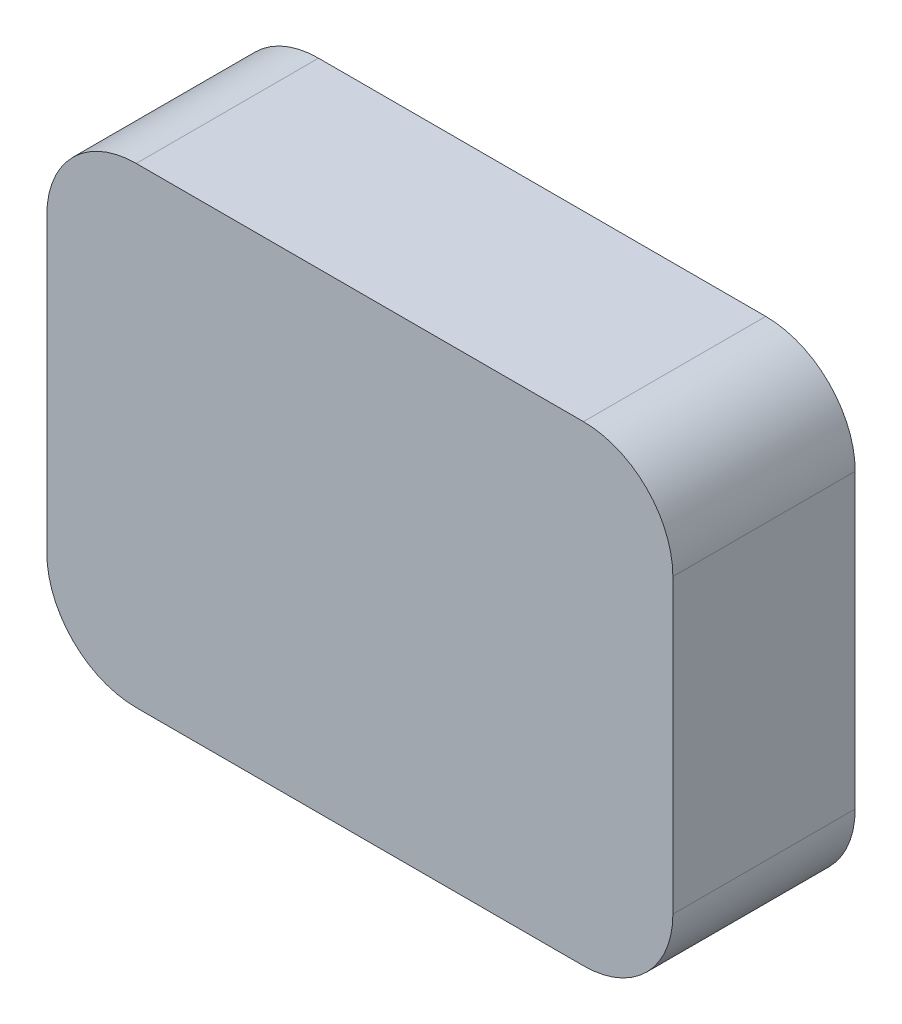
SolidWorks part; units mm, degrees
ref_plane "Plan de face" through (0, 0, 0) normal (0, 0, 1) x (1, 0, 0)
ref_plane "Plan de dessus" through (0, 0, 0) normal (0, 1, 0) x (1, 0, 0)
ref_plane "Plan de droite" through (0, 0, 0) normal (1, 0, 0) x (0, 0, -1)
sketch "Esquisse1" plane through (0, 0, 0) normal (0, 0, 1) x (1, 0, 0)
  line L1 (-26, 27) -> (26, 27)
  line L2 (-36, 17) -> (-36, -17)
  line L3 (-26, -27) -> (26, -27)
  line L4 (36, 17) -> (36, -17)
  line L5 (-36, 27) -> (36, -27) construction
  line L6 (-36, -27) -> (36, 27) construction
  arc A0 (-36, -17) -> (-26, -27) centre (-26, -17) ccw
  arc A1 (26, -27) -> (36, -17) centre (26, -17) ccw
  arc A2 (26, 27) -> (36, 17) centre (26, 17) cw
  arc A3 (-26, 27) -> (-36, 17) centre (-26, 17) ccw
  point P0 (0, 0)
  dimension "D1" = 10
  dimension "D2" = 52
  dimension "D3" = 34
sketch "profil" plane through (0, 0, 0) normal (1, 0, 0) x (0, 0, -1)
  line L0 (0, -25.5219) -> (4.1106, -25.5219)
  line L1 (4.1106, -25.5219) -> (10, -21)
  line L3 (10, -27) -> (0, -27)
  line L4 (0, -27) -> (0, -25.5219)
  line L6 (0, -17) -> (0, -27) construction
  line L7 (0, -27) -> (0, 27) construction
  line L10 (10, -21) -> (10, -27) construction
  line L11 (10, -24) -> (12.7162, -24) construction
  line L12 (10, -25.7405) -> (10, -27) construction
  line L15 (10, -27) -> (10, -26.6)
  line L16 (10, -26.6) -> (9.8, -26.6)
  line L17 (9.8, -26.6) -> (9.8, -25.8)
  line L18 (9.8, -25.8) -> (10, -25.8)
  line L20 (10, -25.8) -> (10, -25.4)
  line L21 (10, -21) -> (10, -21.4)
  line L22 (10, -21.4) -> (9.8, -21.4)
  line L23 (9.8, -21.4) -> (9.8, -22.2)
  line L24 (9.8, -22.2) -> (10, -22.2)
  line L25 (10, -22.2) -> (10, -22.6)
  line L39 (10, -22.6) -> (10.4, -22.6)
  line L54 (10.4, -22.6) -> (10.4, -23)
  line L55 (10.4, -23) -> (10.8, -23)
  line L56 (10.8, -23) -> (10.8, -23.4)
  line L57 (10.8, -23.4) -> (11.2, -23.4)
  line L58 (11.2, -23.4) -> (11.2, -23.8)
  line L59 (11.2, -23.8) -> (11.6, -23.8)
  line L60 (11.6, -23.8) -> (11.6, -24.2)
  line L61 (11.6, -24.2) -> (11.2, -24.2)
  line L62 (11.2, -24.2) -> (11.2, -24.6)
  line L63 (11.2, -24.6) -> (10.8, -24.6)
  line L64 (10.8, -24.6) -> (10.8, -25)
  line L65 (10.8, -25) -> (10.4, -25)
  line L66 (10.4, -25) -> (10.4, -25.4)
  line L67 (10.4, -25.4) -> (10, -25.4)
  point P39 (10.3628, -25)
  dimension "D3" = 10
  dimension "D4" = 6
  dimension "D5" = 0.8
  dimension "D7" = 0.4
  dimension "D1" = 0.4
  dimension "D8" = 0.4
sweep "Balayage1" add profiles "profil" path "Esquisse1"
extrude "Boss.-Extru.1" add sketch "Esquisse1<3>" along normal blind 1.2
sketch "Esquisse1<3>" plane through (0, 0, 0) normal (0, 0, 1) x (1, 0, 0) same geometry as "Esquisse1"
fillet "Congé1" radius 2 9 edges at (-32.0259, 23.0259, 0) (-34.5219, 0, 0) (-32.0259, -23.0259, 0) (-13, -25.5219, 0) (13, -25.5219, 0) (32.0259, -23.0259, 0) (34.5219, 0, 0) (32.0259, 23.0259, 0) (0, 25.5219, 0)
sketch "Esquisse2" plane through (0, 0, 0) normal (0, 0, 1) x (1, 0, 0)
  line L8 (36.4, -17) -> (36.4, 17)
  line L9 (-26, -27.4) -> (26, -27.4)
  line L10 (-36.4, 17) -> (-36.4, -17)
  line L11 (26, 27.4) -> (-26, 27.4)
  line L12 (36.4, -17) -> (36.4, 17)
  line L13 (-26, -27.4) -> (26, -27.4)
  line L14 (-36.4, 17) -> (-36.4, -17)
  line L15 (26, 27.4) -> (-26, 27.4)
  arc A8 (36.4, 17) -> (26, 27.4) centre (26, 17) ccw
  arc A9 (26, -27.4) -> (36.4, -17) centre (26, -17) ccw
  arc A10 (-36.4, -17) -> (-26, -27.4) centre (-26, -17) ccw
  arc A11 (-26, 27.4) -> (-36.4, 17) centre (-26, 17) ccw
  arc A12 (36.4, 17) -> (26, 27.4) centre (26, 17) ccw
  arc A13 (26, -27.4) -> (36.4, -17) centre (26, -17) ccw
  arc A14 (-36.4, -17) -> (-26, -27.4) centre (-26, -17) ccw
  arc A15 (-26, 27.4) -> (-36.4, 17) centre (-26, 17) ccw
  dimension "D1" = 0.4
extrude "Extru.-Mince1" add sketch "Esquisse2" against normal blind 20 and the other way up to surface (1.2 mm away) thin other way up to face at (0, 0, 1.2) thin type one direction reverse wall 0.4
equation "\"buse\"=0.4"
equation "\"coque\"= \"buse\" * 4"
equation "\"diam_silicone\"=3"
equation "\"couche\"=0.2"
equation "\"D1@Boss.-Extru.1\"=\"fond\""
equation "\"fond\"= \"couche\" * 6"
equation "\"D2@Esquisse1\"=\"dim_ext_L@boitier_balaye-1.Part\""
equation "\"D4@profil\"=\"epaisseur_jonction@boitier_balaye-1.Part\""
equation "\"D3@Esquisse1\"=\"dim_ext@boitier_balaye-1.Part\""
equation "\"D8@profil\"=\"couche\"*2"
